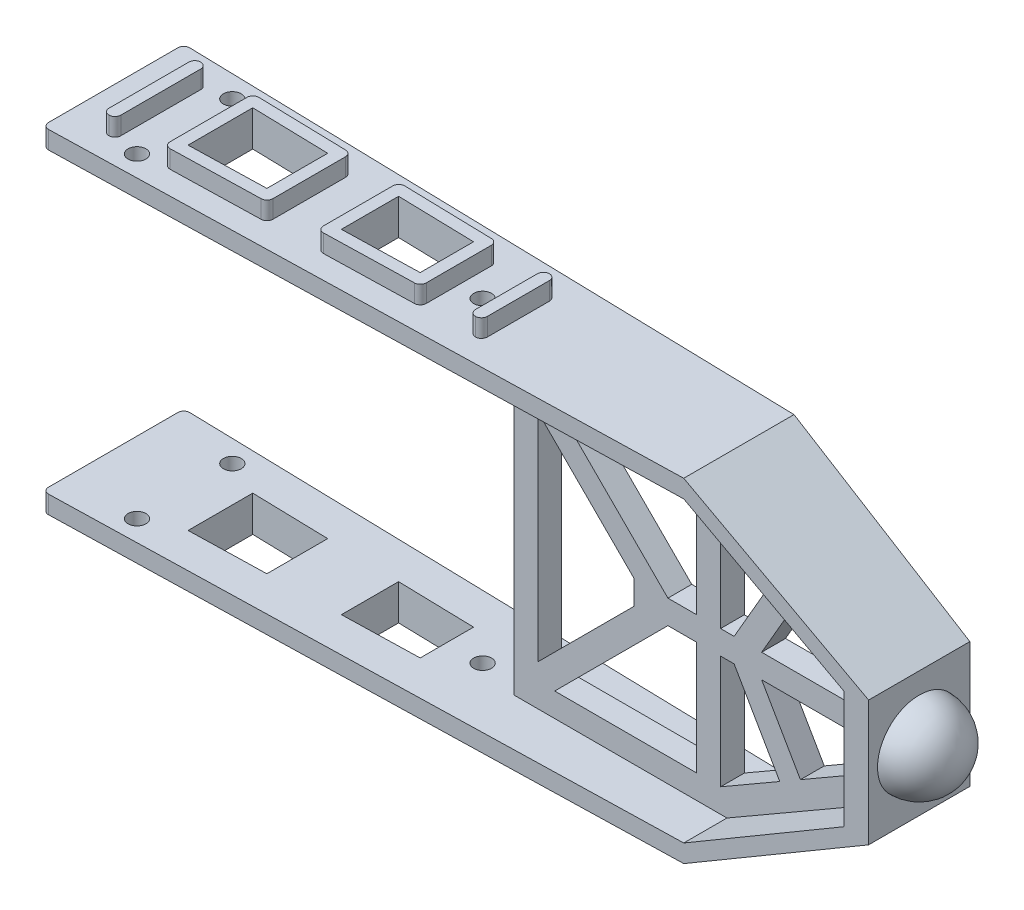
SolidWorks part; units mm, degrees
material "ABS"
ref_plane "前视基准面" through (0, 0, 0) normal (0, 0, 1) x (1, 0, 0)
ref_plane "上视基准面" through (0, 0, 0) normal (0, 1, 0) x (1, 0, 0)
ref_plane "右视基准面" through (0, 0, 0) normal (1, 0, 0) x (0, 0, -1)
sketch "草图1" plane through (0, 0, 0) normal (0, 1, 0) x (1, 0, 0)
  line L0 (-18.5049, 0) -> (123.2148, 0) construction
  line L1 (0.3125, 12.4961) -> (100.25, 9.9969)
  line L6 (0.3125, -12.4961) -> (100.25, -9.9969)
  line L7 (25, 11.8787) -> (25, -11.8787)
  line L8 (100, 10.0031) -> (100, -10.0031)
  line L9 (100, 10.0031) -> (130, 9.2529)
  line L10 (100, -10.0031) -> (130, -9.2529)
  line L11 (130, 9.2529) -> (130, -9.2529)
  line L12 (208.1224, 28.1217) -> (208.1224, 28.4048)
  circle A1 centre (100, 0) radius 10
  circle A2 centre (0, 0) radius 12.5
  dimension "D1" = 25
  dimension "D2" = 20
  dimension "D3" = 100
  dimension "D4" = 25
  dimension "D5" = 100
  dimension "D6" = 130
extrude "凸台-拉伸1" add sketch "草图1" along normal blind 3 contours L7 L0 A1 L8 L1 | L0 L7 L6 L8 A1 | A1 L0 L8 | L0 A1 L8 | L11 L10 L8 L9 region at (57.7952, 0, -5.6151) region at (57.7952, 0, 5.6151) region at (95.7559, 0, -4.2441) region at (95.7559, 0, 4.2441)
sketch "草图2" plane through (0, 3, 0) normal (0, 1, 0) x (1, 0, 0)
  line L0 (-13.5694, 0) -> (149.1216, 0) construction
  circle A1 centre (37, 8) radius 1.5
  circle A2 centre (37, -8) radius 1.5
  circle A3 centre (87, 0) radius 1.5
  dimension "D1" = 8
  dimension "D2" = 3
  dimension "D3" = 3
  dimension "D7" = 3
  dimension "D4" = 37
  dimension "D8" = 87
extrude "切除-拉伸1" cut sketch "草图2" against normal blind 3
sketch "草图3" plane through (0, 3, 0) normal (0, 1, 0) x (1, 0, 0)
  line L0 (41, 7.4773) -> (41, -7.4773)
  line L1 (33, 7.6774) -> (33, -7.6774)
  line L2 (31, 7.7274) -> (31, -7.7274)
  line L3 (43, 7.4273) -> (43, -7.4273)
  line L4 (55.9, 7.1047) -> (55.9, -7.1047)
  line L5 (57.9, 7.0547) -> (57.9, -7.0547)
  line L6 (-13.964, 0) -> (137.4571, 0) construction
  line L7 (66.1, 6.8496) -> (66.1, -6.8496)
  line L8 (68.1, 6.7996) -> (68.1, -6.7996)
  line L9 (81, 6.477) -> (81, -6.477)
  line L10 (31, 7.7274) -> (93, 6.1769)
  line L11 (83, 6.427) -> (83, -6.427)
  line L12 (91, 6.2269) -> (91, -6.2269)
  line L13 (93, 4.1763) -> (93, -4.1763)
  line L14 (31, 5.7268) -> (93, 4.1763)
  line L15 (25, 11.8787) -> (130, 9.2529) construction
  line L16 (31, -5.7268) -> (93, -4.1763)
  line L17 (31, -7.7274) -> (93, -6.1769)
  line L18 (93, 4.1763) -> (93, 6.1769)
  line L19 (93, -4.1763) -> (93, -6.1769)
  dimension "D1" = 31
  dimension "D2" = 33
  dimension "D3" = 41
  dimension "D4" = 43
  dimension "D5" = 55.9
  dimension "D6" = 57.9
  dimension "D7" = 66.1
  dimension "D8" = 68.1
  dimension "D9" = 81
  dimension "D10" = 83
  dimension "D11" = 91
  dimension "D12" = 93
  dimension "D13" = 4
  dimension "D14" = 2
extrude "凸台-拉伸2" add sketch "草图3" along normal blind 3 contours L2 L14 L1 L10 | L2 L6 L1 L14 | L6 L2 L16 L1 | L2 L17 L1 L16 | L0 L14 L3 L10 | L0 L6 L3 L14 | L6 L0 L16 L3 | L0 L17 L3 L16 | L3 L14 L4 L10 | L3 L17 L4 L16 | L4 L14 L5 L10 | L4 L6 L5 L14 | L6 L4 L16 L5 | L4 L17 L5 L16 | L7 L14 L8 L10 | L7 L6 L8 L14 | L6 L7 L16 L8 | L7 L17 L8 L16 | L8 L14 L9 L10 | L8 L17 L9 L16 | L9 L17 L11 L16 | L6 L9 L16 L11 | L9 L6 L11 L14 | L9 L14 L11 L10 | L14 L18 L10 L12 | L12 L6 L13 L14 | L6 L12 L16 L13 | L19 L16 L12 L17 region at (42, 3, -6.452) region at (41.9985, 3, -2.7259) region at (32, 3, -6.7021) region at (49.45, 3, -6.2657) region at (41.9985, 3, 2.7259) region at (31.9985, 3, -2.8509) region at (56.9, 3, -6.0794) region at (42, 3, 6.452) region at (31.9985, 3, 2.8509) region at (56.8984, 3, -2.5396) region at (32, 3, 6.7021) region at (49.45, 3, 6.2657) region at (56.8984, 3, 2.5396) region at (67.1, 3, -5.8243) region at (56.9, 3, 6.0794) region at (67.0983, 3, -2.412) region at (74.55, 3, -5.638) region at (67.0983, 3, 2.412) region at (82, 3, -5.4517) region at (67.1, 3, 5.8243) region at (81.9981, 3, -2.2257) region at (74.55, 3, 5.638) region at (81.9981, 3, 2.2257) region at (92, 3, -5.2016) region at (82, 3, 5.4517) region at (91.998, 3, -2.1007) region at (91.998, 3, 2.1007) region at (92, 3, 5.2016)
fillet "圆角1" radius 1 16 edges at (91, 4.5, 6.2269) (93, 4.5, 6.1769) (93, 4.5, -6.1769) (91, 4.5, -6.2269) (83, 4.5, -6.427) (83, 4.5, 6.427) (66.1, 4.5, 6.8496) (66.1, 4.5, -6.8496) (57.9, 4.5, -7.0547) (57.9, 4.5, 7.0547) (41, 4.5, -7.4773) (41, 4.5, 7.4773) (33, 4.5, 7.6774) (31, 4.5, 7.7274) (33, 4.5, -7.6774) (31, 4.5, -7.7274)
fillet "圆角2" radius 1 2 edges at (25, 1.5, 11.8787) (25, 1.5, -11.8787)
sketch "草图4" plane through (0, 3, 0) normal (0, 1, 0) x (1, 0, 0)
  line L0 (43, 5.4267) -> (55.9, 5.1041)
  line L1 (55.9, 5.1041) -> (55.9, -5.1041) construction
  line L2 (55.9, 5.1041) -> (55.9, -5.1041) construction
  line L3 (55.9, 5.1041) -> (55.9, -5.1041)
  line L4 (55.9, -5.1041) -> (43, -5.4267)
  line L5 (43, -5.4267) -> (43, 5.4267)
  line L6 (68.1, 4.799) -> (81, 4.4764)
  line L7 (81, 4.4764) -> (81, -4.4764)
  line L8 (81, 4.4764) -> (81, -4.4764) construction
  line L9 (81, 4.4764) -> (81, -4.4764) construction
  line L10 (81, -4.4764) -> (68.1, -4.799)
  line L11 (68.1, -4.799) -> (68.1, 4.799)
extrude "切除-拉伸2" cut sketch "草图4" against normal blind 3
sketch "草图5" plane through (0.3125, 0, 12.4961) normal (0.025, 0, 0.9997) x (0.9997, 0, -0.025)
  line L0 (129.728, 1.5) -> (213.6054, -46.9266) construction
  line L1 (129.728, 3) -> (129.728, 0) construction
  line L3 (129.728, 3) -> (160, -14.4775)
  line L4 (129.728, 0) -> (160, -17.4775)
  line L5 (160, -14.4775) -> (160, -17.4775)
  line L6 (25.7205, 0) -> (129.728, 0) construction
  line L10 (129.728, 3) -> (25.7205, 3)
  line L11 (25.7205, 3) -> (25.7205, 0)
  line L12 (25.7205, 0) -> (129.728, 0)
  line L13 (129.728, 0) -> (129.728, 3)
  line L17 (129.728, 0) -> (129.728, 3)
  dimension "D1" = 210
  dimension "D2" = 160
  dimension "D3" = 0
extrude "凸台-拉伸3" add sketch "草图5" along direction (0, 0, 1) on the side against the normal up to surface (18.5058 mm away) up to face at (78.0125, 1.5, -10.553)
ref_plane "基准面1" through (0, -25, 0) normal (0, -1, 0) x (-1, 0, 0)
sketch "草图6" plane through (0, -25, 0) normal (0, -1, 0) x (-1, 0, 0)
  line L0 (12.6737, 0) -> (-192.2281, 0) construction
  line L5 (-94.2625, -2) -> (-94.2625, 2)
  line L6 (-94.2625, 2) -> (-160.2625, 2)
  line L9 (-160.2625, -2) -> (-94.2625, -2)
  line L14 (-160.2625, 2) -> (-160.2625, -2)
  line L15 (-160.2625, 8.4961) -> (-160.2625, -8.4961) construction
  dimension "D2" = 4
  dimension "D4" = 66
extrude "凸台-拉伸4" add sketch "草图6" against normal up to body separate body contours L6 L14 L9 L5
mirror "镜向21" about plane through (0, -25, 0) normal (0, -1, 0) of bodies 113
sketch "草图8" plane through (0, 0, -2) normal (0, 0, -1) x (-1, 0, 0)
  line L1 (-160.2625, -17.4775) -> (-160.2625, -32.5225)
  line L2 (-160.2625, -32.5225) -> (-156.2625, -34.8326)
  line L3 (-130, -50) -> (-160.2625, -32.5225) construction
  line L4 (-156.2625, -34.8326) -> (-156.2625, -15.1674)
  line L5 (-130, 0) -> (-160.2625, -17.4775) construction
  line L6 (-156.2625, -15.1674) -> (-160.2625, -17.4775)
  dimension "D1" = 4
extrude "凸台-拉伸6" add sketch "草图8" along normal up to surface (6.4961 mm away) up to face at (105.4292, -4.3258, -9.8674)
sketch "草图9" plane through (0, 0, 2) normal (0, 0, 1) x (1, 0, 0)
  line L0 (160.2625, -17.4775) -> (156.2625, -15.1674)
  line L1 (130, 0) -> (160.2625, -17.4775) construction
  line L2 (156.2625, -15.1674) -> (156.2625, -34.8326)
  line L3 (130, -50) -> (160.2625, -32.5225) construction
  line L4 (156.2625, -34.8326) -> (160.2625, -32.5225)
  line L5 (160.2625, -32.5225) -> (160.2625, -17.4775)
  dimension "D1" = 4
extrude "凸台-拉伸7" add sketch "草图9" along normal up to surface (6.5961 mm away) up to face at (105.4292, -4.3258, 9.8674)
sketch "草图10" plane through (0, 0, -2) normal (0, 0, -1) x (-1, 0, 0)
  line L0 (-152.2625, -17.4764) -> (-152.2625, -32.5236)
  line L1 (-152.2625, -32.5236) -> (-128.9279, -46)
  line L2 (-128.9279, -46) -> (-98.2625, -46)
  line L3 (-98.2625, -46) -> (-98.2625, -4)
  line L4 (-98.2625, -4) -> (-128.9279, -4)
  line L5 (-128.9279, -4) -> (-152.2625, -17.4764)
  line L6 (-130, 0) -> (-156.2625, -15.1674) construction
  line L7 (-130, -50) -> (-156.2625, -34.8326) construction
  line L8 (-26.025, 0) -> (-130, 0) construction
  line L9 (-94.2625, -50) -> (-130, -50) construction
  line L10 (-94.2625, 0) -> (-94.2625, -50) construction
  line L11 (-156.2625, -15.1674) -> (-130, 0) construction
  line L12 (-156.2625, -34.8326) -> (-156.2625, -15.1674) construction
  line L13 (-152.2625, -23) -> (-98.2625, -23)
  line L14 (-98.2625, -27) -> (-152.2625, -27)
  line L15 (-13.0387, -25) -> (13.0387, -25) construction
  line L16 (-141.8492, -8.567) -> (-128.9279, -30.9402) construction
  line L17 (-142.3271, -11.7385) -> (-135.8232, -23)
  line L18 (-138.8633, -9.738) -> (-131.2041, -23)
  line L19 (-119.5563, -36.5) -> (-119.5587, -36.5)
  line L20 (-152.2625, -25) -> (-76.4261, -25) construction
  line L21 (-142.3271, -38.2615) -> (-135.8232, -27)
  line L22 (-138.8633, -40.262) -> (-131.2041, -27)
  line L23 (-128.9279, -4) -> (-128.9279, -23)
  line L24 (-124.9279, -4) -> (-124.9279, -23)
  line L25 (-128.9279, -46) -> (-128.9279, -27)
  line L26 (-124.9279, -46) -> (-124.9279, -27)
  line L27 (-98.2625, -4) -> (-115.7501, -21.4876) construction
  line L28 (-101.0909, -4) -> (-120.0909, -23)
  line L29 (-98.2625, -6.8284) -> (-114.4341, -23)
  line L30 (-98.2625, -43.1716) -> (-114.4341, -27)
  line L31 (-101.0909, -46) -> (-120.0909, -27)
  line L32 (-114.4341, -23) -> (-114.4341, -27)
  point P34 (-140.5952, -10.7382)
  dimension "D1" = 4
  dimension "D2" = 4
  dimension "D3" = 4
  dimension "D4" = 4
  dimension "D5" = 4
  dimension "D6" = 4
  dimension "D7" = 2
  dimension "D8" = 2
  dimension "D9" = 4
  dimension "D10" = 4
  dimension "D11" = 4
  dimension "D12" = 45
  dimension "D13" = 2
extrude "切除-拉伸3" cut sketch "草图10" against normal blind 4 contours L3 L29 L13 | L13 L32 L14 L3 | L30 L3 L14 | L2 L31 L14 L26 | L28 L4 L24 L13 | L23 L5 L18 L13 | L17 L5 L0 L13 | L1 L21 L14 L0 | L1 L25 L14 L22 region at (144.7239, -18.8252, -2) region at (144.7239, -31.1748, -2) region at (132.3443, -13.1191, -2) region at (132.3443, -36.8809, -2) region at (116.7103, -11.4017, -2) region at (116.7103, -38.5983, -2) region at (103.653, -17.6095, -2) region at (106.3483, -25, -2) region at (103.653, -32.3905, -2)
sketch "草图11" plane through (0, 0, 0) normal (0, 0, 1) x (1, 0, 0)
  line L0 (160.2625, -25) -> (177.6906, -25) construction
  line L1 (160.2625, -35.5225) -> (160.2625, -14.4775) construction
  line L2 (-13.0387, -25) -> (13.0387, -25) construction
  line L3 (160.2625, -32) -> (160.2625, -18)
  line L4 (167.2625, -25) -> (160.2625, -25)
  line L5 (160.2625, -25) -> (160.2625, -18)
  arc A0 (160.2625, -32) -> (160.2625, -18) centre (160.2625, -25) ccw
  dimension "D1" = 7
revolve "旋转1" add sketch "草图11" angle 360 about L0 region at (163.2334, -22.0291, 0)
